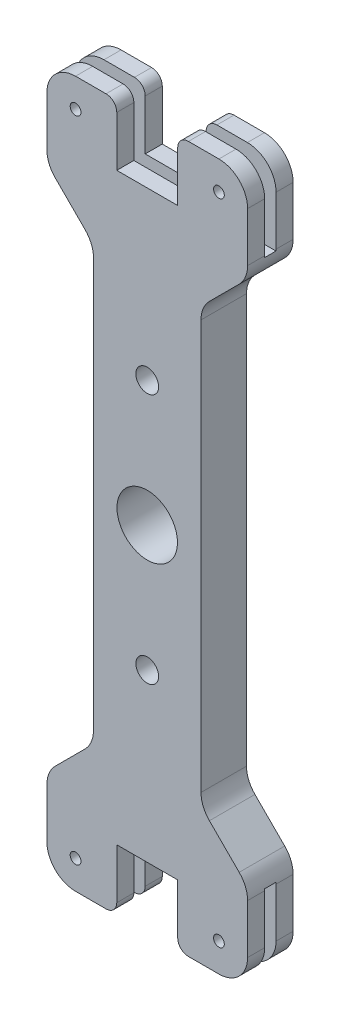
SolidWorks part; units mm, degrees
ref_plane "Front Plane" through (0, 0, 0) normal (0, 0, 1) x (1, 0, 0)
ref_plane "Top Plane" through (0, 0, 0) normal (0, 1, 0) x (1, 0, 0)
ref_plane "Right Plane" through (0, 0, 0) normal (1, 0, 0) x (0, 0, -1)
sketch "Sketch1" plane through (0, 0, 0) normal (0, 0, 1) x (1, 0, 0)
  line L1 (0, -5.2388) -> (0, 5.2388) construction
  line L2 (5.2388, 0) -> (-5.2388, 0) construction
  line L3 (-28, 73.3978) -> (-28, 90.475)
  line L4 (-20, 98.475) -> (-11.5, 98.475)
  line L5 (28, 90.475) -> (28, 73.3978)
  line L6 (28, 73.3978) -> (15, 60.3978)
  line L7 (15, 60.3978) -> (15, -60.3978)
  line L13 (-15, -60.3978) -> (-15, 60.3978)
  line L14 (-15, 60.3978) -> (-28, 73.3978)
  line L15 (0, -1000) -> (0, 49000) construction
  line L16 (-1000, 0) -> (49000, 0) construction
  line L17 (-8.5, 95.475) -> (-8.5, 81.475)
  line L18 (-8.5, 81.475) -> (8.5, 81.475)
  line L19 (8.5, 81.475) -> (8.5, 95.475)
  line L20 (11.5, 98.475) -> (20, 98.475)
  line L21 (-20, 98.475) -> (-20, 90.475) construction
  line L22 (-20, 90.475) -> (-28, 90.475) construction
  line L23 (-8.5, 81.475) -> (-22.2886, 67.6864) construction
  line L24 (-8.5, 81.475) -> (-28, 81.475) construction
  line L25 (28, -73.3978) -> (15, -60.3978)
  line L26 (28, -90.475) -> (28, -73.3978)
  line L27 (11.5, -98.475) -> (20, -98.475)
  line L28 (8.5, -81.475) -> (8.5, -95.475)
  line L29 (-8.5, -81.475) -> (8.5, -81.475)
  line L30 (-8.5, -95.475) -> (-8.5, -81.475)
  line L31 (-20, -98.475) -> (-11.5, -98.475)
  line L32 (-28, -73.3978) -> (-28, -90.475)
  line L33 (-15, -60.3978) -> (-28, -73.3978)
  circle A0 centre (0, 0) radius 8.4375
  circle A1 centre (-20, 90.475) radius 1.5
  circle A3 centre (20, 90.475) radius 1.5
  circle A4 centre (20, -90.475) radius 1.5
  circle A5 centre (-20, -90.475) radius 1.5
  arc A6 (-28, 90.475) -> (-20, 98.475) centre (-20, 90.475) cw
  arc A7 (20, 98.475) -> (28, 90.475) centre (20, 90.475) cw
  arc A8 (20, -98.475) -> (28, -90.475) centre (20, -90.475) ccw
  arc A9 (-28, -90.475) -> (-20, -98.475) centre (-20, -90.475) ccw
  arc A10 (-8.5, -95.475) -> (-11.5, -98.475) centre (-11.5, -95.475) cw
  arc A11 (11.5, -98.475) -> (8.5, -95.475) centre (11.5, -95.475) cw
  arc A12 (8.5, 95.475) -> (11.5, 98.475) centre (11.5, 95.475) cw
  arc A13 (-8.5, 95.475) -> (-11.5, 98.475) centre (-11.5, 95.475) ccw
  point P22 (0, 81.475)
  point P39 (15, 0)
  point P51 (-15, 0)
  point P53 (-8.5, -98.475)
  point P56 (8.5, -98.475)
  point P59 (8.5, 98.475)
  point P62 (-8.5, 98.475)
  dimension "D1" = 16.875
  dimension "D9" = 3
  dimension "D3" = 30
  dimension "D4" = 17
  dimension "D5" = 40
  dimension "D6" = 8
  dimension "D7" = 180.95
  dimension "D8" = 45
  dimension "D10" = 17
extrude "Boss-Extrude1" add sketch "Sketch1" along normal mid plane 12.7
fillet "Fillet1" radius 8 8 edges at (-28, 73.3978, 0) (-15, 60.3978, 0) (-28, -73.3978, 0) (-15, -60.3978, 0) (15, -60.3978, 0) (28, -73.3978, 0) (28, 73.3978, 0) (15, 60.3978, 0)
sketch "Sketch3" plane through (0, 98.475, 0) normal (0, 1, 0) x (1, 0, 0)
  line L0 (-28, -6.35) -> (-28, 6.35) construction
  line L1 (28, 1.5875) -> (-28, 1.5875)
  line L2 (28, 1.5875) -> (28, -1.5875)
  line L3 (28, -1.5875) -> (-28, -1.5875)
  line L4 (-28, 1.5875) -> (-28, -1.5875)
  line L5 (28, 1.5875) -> (-28, -1.5875) construction
  line L6 (28, -1.5875) -> (-28, 1.5875) construction
  point P0 (0, 0)
  dimension "D1" = 3.175
extrude "Cut-Extrude1" cut sketch "Sketch3" against normal blind 22.22
mirror "Mirror1" about plane through (0, 0, 0) normal (0, 1, 0) of "Cut-Extrude1"
sketch "Sketch4" plane through (0, 0, 6.35) normal (0, 0, 1) x (1, 0, 0)
  line L0 (0, 35) -> (0, -35) construction
  circle A0 centre (0, 35) radius 3.175
  circle A1 centre (0, -35) radius 3.175
  point P4 (0, 0)
  dimension "D1" = 6.35
  dimension "D2" = 70
extrude "Cut-Extrude2" cut sketch "Sketch4" against normal through all
equation "\"D1@Fillet1\"=\"D6@Sketch1\""
equation "\"Shaft Size\" = 5in / 8"
equation "\"Bearing Screw Size\"= 1in / 4"
equation "\"Bearing Screw Spacing\"= 70mm"
equation "\"D1@Sketch1\"= \"Shaft Size\" + 1mm"
equation "\"D1@Sketch4\"= \"Bearing Screw Size\""
equation "\"D2@Sketch4\"= \"Bearing Screw Spacing\""
equation "\"Plate Thickness\"= 1in / 2"
equation "\"D1@Boss-Extrude1\"=\"Plate Thickness\""
